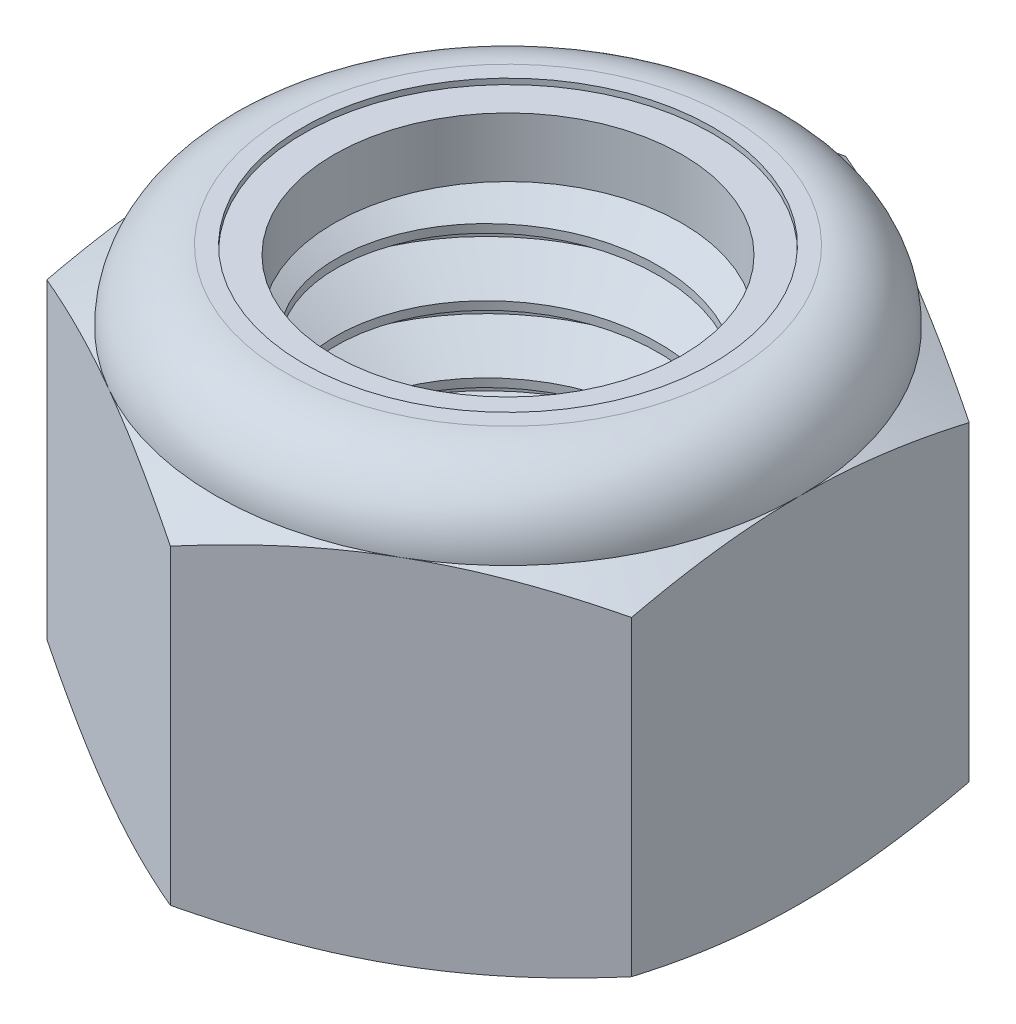
SolidWorks part; units mm, degrees
note: '?' marks a value the reader was unsure of.
ref_plane "Front" through (0, 0, 0) normal (0, 0, 1) x (1, 0, 0)
ref_plane "Top" through (0, 0, 0) normal (0, 1, 0) x (1, 0, 0)
ref_plane "Right" through (0, 0, 0) normal (1, 0, 0) x (0, 0, -1)
sketch "Sketch8" plane through (0, 0, 0) normal (1, 0, 0) x (0, 0, -1)
  line L0 (0, 0) -> (0, 11.5094) construction
  line L1 (7.9375, 0) -> (-7.9375, 0) construction
  line L2 (-5.5562, 11.5094) -> (5.5562, 11.5094) construction
  line L3 (5.5562, 11.5094) -> (5.5562, 9.6951) construction
sketch "Sketch1" plane through (0, 0, 0) normal (0, 1, 0) x (1, 0, 0)
  line L1 (0, 9.1654) -> (-7.9375, 4.5827)
  line L2 (-7.9375, 4.5827) -> (-7.9375, -4.5827)
  line L3 (-7.9375, -4.5827) -> (0, -9.1654)
  line L4 (0, -9.1654) -> (7.9375, -4.5827)
  line L5 (7.9375, -4.5827) -> (7.9375, 4.5827)
  line L6 (7.9375, 4.5827) -> (0, 9.1654)
  circle A0 centre (0, 0) radius 7.9375 construction
  circle A1 centre (0, 0) radius 5.5562
extrude "Extrude1" add sketch "Sketch1" along normal up to vertex (11.5094 mm away) up to point (0, 11.5094, 0)
sketch "Sketch5" plane through (0, 0, 0) normal (1, 0, 0) x (0, 0, -1)
  line L0 (0, 0) -> (7.9375, 0)
  line L1 (7.9375, 0) -> (9.1654, 0.5726)
  line L2 (9.1654, 0.5726) -> (9.1654, 9.0186)
  line L3 (9.1654, 9.0186) -> (7.9375, 9.5911)
  line L4 (6.0193, 11.5094) -> (6.0193, 12.7794)
  line L5 (6.0193, 12.7794) -> (10.4354, 12.7794)
  line L6 (10.4354, 12.7794) -> (10.4354, -1.27)
  line L7 (10.4354, -1.27) -> (0, -1.27)
  line L8 (0, -1.27) -> (0, 0)
  line L9 (7.9375, 9.5911) -> (7.9375, 0) construction
  line L12 (9.1654, 11.5094) -> (9.1654, 0) construction
  line L13 (9.1654, 5.7547) -> (10.4354, 5.7547) construction
  line L15 (0, 0) -> (0, 12.7794) construction
  line L18 (7.9375, 0) -> (-7.9375, 0) construction
  line L19 (4.5827, 11.5094) -> (9.1654, 11.5094) construction
  line L20 (0, 12.7794) -> (6.0193, 12.7794) construction
  line L21 (4.5827, 0) -> (9.1654, 0) construction
  arc A0 (7.9375, 9.5911) -> (6.0193, 11.5094) centre (6.0193, 9.5911) ccw
  dimension "D1" = 25
  dimension "D2" = 1.27
  dimension "D4" = 1.9182
revolve "Cut-Revolve3" cut sketch "Sketch5" angle 360 about L15
sketch "Sketch4" plane through (0, 0, 0) normal (1, 0, 0) x (0, 0, -1)
  line L0 (0, 9.5911) -> (6.1119, 9.5911)
  line L1 (6.1119, 9.5911) -> (0, 6.7411)
  line L3 (0, 2.85) -> (6.1119, 0)
  line L4 (6.1119, 0) -> (0, 0)
  line L5 (0, 0) -> (0, 9.5911) construction
  line L10 (0, 0) -> (0, 11.5094) construction
  line L11 (0, 2.85) -> (0, 0)
  line L12 (0, 9.5911) -> (0, 6.7411)
  line L13 (6.8741, 9.5911) -> (0, 9.5911) construction
  dimension "D1" = 25
  dimension "D2" = 12.2237
sketch "Sketch6" plane through (0, 0, 0) normal (1, 0, 0) x (0, 0, -1)
  line L0 (0, 9.5911) -> (7.7851, 9.5911)
  line L1 (6.0193, 11.357) -> (3.0096, 11.357)
  line L2 (0, 12.7794) -> (0, 9.5911)
  line L3 (3.0096, 12.7794) -> (0, 12.7794)
  line L4 (0, 12.7794) -> (6.0193, 12.7794) construction
  line L5 (0, 0) -> (0, 12.7794) construction
  line L6 (0, 12.7794) -> (0, 0) construction
  line L7 (3.0096, 11.357) -> (3.0096, 12.7794)
  line L8 (6.0193, 11.5094) -> (6.0193, 11.357) construction
  line L9 (3.0096, 11.357) -> (0, 11.357) construction
  line L10 (0, 11.357) -> (0, 6.7411) construction
  arc A0 (7.7851, 9.5911) -> (6.0193, 11.357) centre (6.0193, 9.5911) ccw
  arc A1 (7.9375, 9.5911) -> (6.0193, 11.5094) centre (6.0193, 9.5911) ccw construction
  dimension "D1" = 0.1524
revolve "Cut-Revolve4" cut sketch "Sketch6" angle 360 about L6
revolve "Cut-Revolve2" cut sketch "Sketch4" angle 360 about L5
sketch "Sketch7" plane through (0, 0, 0) normal (1, 0, 0) x (0, 0, -1)
  line L0 (4.7228, 9.6673) -> (7.7072, 9.6673)
  line L1 (6.0193, 11.2808) -> (4.7228, 11.2808)
  line L2 (4.7228, 11.2808) -> (4.7228, 9.6673)
  line L3 (4.7228, 9.6673) -> (0, 9.6673) construction
  line L4 (0, 9.6673) -> (0, 11.2808) construction
  line L5 (0, 11.2808) -> (4.7228, 11.2808) construction
  line L6 (4.7228, 9.6673) -> (4.7228, 9.5911) construction
  line L7 (0, 9.5911) -> (7.7851, 9.5911) construction
  line L8 (6.0193, 11.2808) -> (6.0193, 11.357) construction
  arc A0 (7.7072, 9.6673) -> (6.0193, 11.2808) centre (6.0193, 9.5911) ccw
  arc A2 (7.7851, 9.5911) -> (6.0193, 11.357) centre (6.0193, 9.5911) ccw construction
  dimension "D1" = 0.0762
  dimension "D2" = 9.4456
revolve "Revolve2" add sketch "Sketch7" angle 360 about L4
sketch "Sketch2" plane through (0, 0, 0) normal (1, 0, 0) x (0, 0, -1)
  line L0 (-5.5562, 0) -> (-5.5562, 9.5911) construction
  line L1 (0, 0) -> (5.5562, 0)
  line L2 (0, 0) -> (0, 9.5911)
  line L3 (0, 9.5911) -> (5.5562, 9.5911)
  line L4 (5.5562, 0) -> (5.5562, 9.5911)
  line L6 (6.8741, 9.5911) -> (7.9375, 9.5911) construction
  line L7 (0, -5.5562) -> (0, 0) construction
revolve "Revolve1" add sketch "Sketch2" angle 360 about L7
sketch "Sketch9" plane through (0, 0, 0) normal (1, 0, 0) x (0, 0, -1)
  line L0 (5.7527, 11.292) -> (5.7527, 9.4778) construction
  line L1 (5.7527, 9.4778) -> (4.1814, 10.3849) construction
  line L2 (4.1814, 10.3849) -> (5.7527, 11.292) construction
  line L3 (4.3778, 10.4983) -> (4.3778, 10.2715) construction
  line L4 (5.5562, 11.1786) -> (5.5562, 9.5911) construction
  line L5 (4.1814, 10.3849) -> (4.3778, 10.3849) construction
  line L6 (5.5562, 10.3849) -> (5.7527, 10.3849) construction
  line L7 (5.6545, 10.3849) -> (5.6545, 11.2353) construction
  line L8 (5.7527, 9.4778) -> (5.6545, 11.2353)
  line L9 (5.6545, 11.2353) -> (4.3778, 10.4983)
  line L10 (4.3778, 10.4983) -> (4.3778, 10.2715)
  line L11 (4.3778, 10.2715) -> (5.7527, 9.4778)
  dimension "D1" = 1.8143
  dimension "D2" = 0.2268
sketch "Sketch10" plane through (0, 9.5911, 0) normal (0, 1, 0) x (1, 0, 0)
  circle A1 centre (0, 0) radius 5.5562
  circle A2 centre (0, 0) radius 5.5562
  dimension "D1" = 0
curve "Helix/Spiral1" pitch 1.8143 height 13.3237 turns 7.3438
sweep "Cut-Sweep1" cut profiles "Sketch9" path "Helix/Spiral1" align with end faces yes
sketch "Sketch11" plane through (0, 0, 0) normal (1, 0, 0) x (0, 0, -1)
  line L0 (0, 0) -> (0, 11.5094) construction
  line L1 (7.9375, 0) -> (-7.9375, 0) construction
  line L4 (0, 11.5094) -> (0, 0) construction
  line L5 (0, 5.7547) -> (5.5563, 5.7547) construction
  line L6 (0, 0) -> (6.1119, 0)
  line L7 (0, 2.85) -> (0, 0)
  line L8 (6.1119, 0) -> (0, 2.85)
  dimension "D1" = 12.2237
  dimension "D2" = 25
revolve "Revolve3" add sketch "Sketch11" angle 360 about L4
sketch "Sketch12" plane through (0, 0, 0) normal (1, 0, 0) x (0, 0, -1)
  line L0 (6.1119, 9.5911) -> (0, 9.5911)
  line L1 (0, 9.5911) -> (0, 0)
  line L2 (0, 0) -> (6.1119, 0)
  line L3 (7.9375, 0) -> (-7.9375, 0) construction
  line L4 (6.1119, 0) -> (6.1119, 9.5911)
  line L5 (-6.1119, 0) -> (6.1119, 0) construction
revolve "Revolve4" add sketch "Sketch12" angle 360 about L0
combine bodies "Combine1" operation type subtract main body 136 bodies to subtract 133
ref_plane "Contact Plane 1" through (0, 0, 0) normal (0, -1, 0) x (1, 0, 0)
ref_axis "Center Axis 1" through (0, -2.1015, 0) along (0, 1, 0)?
equation "\"D4@Sketch5\"=\"Height@Sketch8\"/6"
equation "\"D1@Sketch9\"=\"Thread Pitch@Sketch8\""
equation "\"D2@Sketch9\"=\"Thread Pitch@Sketch8\"/8"
equation "\"D4@Helix/Spiral1\"=\"Thread Pitch@Sketch8\""
equation "\"D3@Helix/Spiral1\"=\"Thread Pitch@Sketch8\"+\"Height@Sketch8\""
equation "\"D2@Sketch4\"=\"Thread Dia@Sketch8\"*1.1"
equation "\"D1@Sketch11\"=\"Thread Dia@Sketch8\"*1.1"
equation "\"D2@Sketch7\"=\"Thread Dia@Sketch8\"*.85"
